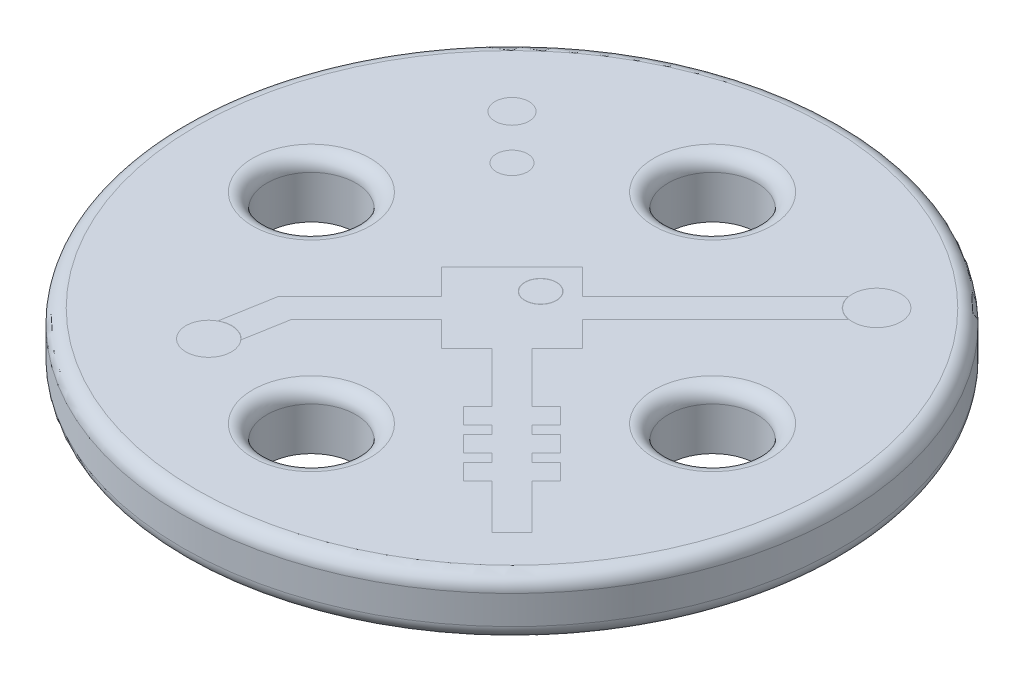
SolidWorks part; units mm, degrees
other "graphite_1"
other "blue_2"
other "white_6"
other "white_7"
other "white_10"
other "white_4"
other "white_2"
other "blue_1"
other "white_3"
other "white_9"
other "white_8"
other "white_5"
other "white"
ref_plane "Front Plane" through (0, 0, 0) normal (0, 0, 1) x (1, 0, 0)
ref_plane "Top Plane" through (0, 0, 0) normal (0, 1, 0) x (1, 0, 0)
ref_plane "Right Plane" through (0, 0, 0) normal (1, 0, 0) x (0, 0, -1)
sketch "Sketch1" plane through (0, 0, 0) normal (0, 1, 0) x (1, 0, 0)
  line L0 (0, 7) -> (0, 0) construction
  circle A0 centre (0, 0) radius 11.5
  circle A1 centre (0, 7) radius 1.55
  circle A2 centre (7, 0) radius 1.55
  circle A3 centre (0, -7) radius 1.55
  circle A4 centre (-7, 0) radius 1.55
  point P14 (0, 0)
  dimension "D1" = 23
  dimension "D2" = 3.1
  dimension "D3" = 7
  dimension "D4" = 4
extrude "Boss-Extrude1" add sketch "Sketch1" along normal blind 2
fillet "Fillet1" radius 0.5 6 edges at (-7, 2, 1.55) (7, 2, 1.55) (0, 2, 11.5) (0, 2, -5.45) (0, 2, 8.55) (0, 0, 11.5)
sketch "Sketch2" [suppressed] plane through (0, 2, 0) normal (0, 1, 0) x (1, 0, 0)
  line L0 (-2.4749, -2.4749) -> (2.4749, 2.4749) construction
  line L3 (-4.2426, -0.7071) -> (0.7071, 4.2426) construction
  line L4 (-0.7071, -4.2426) -> (4.2426, 0.7071) construction
  line L5 (0, 0) -> (23.072, 0) construction
  line L6 (-6.364, -2.1213) -> (-2.1213, -6.364) construction
  line L7 (-2.1213, -6.364) -> (6.364, 2.1213) construction
  line L8 (6.364, 2.1213) -> (2.1213, 6.364) construction
  line L9 (2.1213, 6.364) -> (-6.364, -2.1213) construction
  line L10 (-6.364, -2.1213) -> (6.364, 2.1213) construction
  line L11 (2.1213, 6.364) -> (6.364, 2.1213)
  line L12 (6.364, 2.1213) -> (4.9497, 0.7071)
  line L13 (2.1213, 6.364) -> (0.7071, 4.9497)
  line L14 (-6.364, -2.1213) -> (-4.9497, -0.7071)
  line L15 (-6.364, -2.1213) -> (-2.1213, -6.364)
  line L16 (-2.1213, -6.364) -> (-0.7071, -4.9497)
  circle A0 centre (-7, 0) radius 2.75 construction
  circle A1 centre (0, 7) radius 2.75 construction
  circle A2 centre (7, 0) radius 2.75 construction
  circle A3 centre (0, -7) radius 2.75 construction
  arc A6 (-4.2426, -0.7071) -> (-0.7071, -4.2426) centre (-2.4749, -2.4749) ccw construction
  arc A7 (4.2426, 0.7071) -> (0.7071, 4.2426) centre (2.4749, 2.4749) ccw construction
  circle A8 centre (0, 0) radius 5 construction
  arc A10 (-0.7071, -4.9497) -> (4.9497, 0.7071) centre (0, 0) ccw
  arc A12 (0.7071, 4.9497) -> (-4.9497, -0.7071) centre (0, 0) ccw
  point P13 (0, 0)
  dimension "D1" = 5.5
  dimension "D2" = 12
  dimension "D3" = 5
  dimension "D7" = 10
  dimension "D4" = 45
  dimension "D5" = 6
  dimension "D6" = 12
extrude "Cable hole" [suppressed] cut sketch "Sketch2" against normal through all
fillet "Fillet2" [suppressed] radius 1
sketch "GL_F_side_blue" plane through (0, 0, 0) normal (0, 1, 0) x (1, 0, 0)
  line L0 (4.1012, -5.7912) -> (3.5426, -5.2326)
  line L1 (3.5426, -5.2326) -> (4.0376, -4.7376)
  line L2 (4.0376, -4.7376) -> (3.7477, -4.4477)
  line L3 (3.7477, -4.4477) -> (3.2527, -4.9427)
  line L4 (3.2527, -4.9427) -> (2.6941, -4.3841)
  line L5 (2.6941, -4.3841) -> (3.1891, -3.8891)
  line L6 (3.1891, -3.8891) -> (1.2092, -1.9092)
  line L7 (1.2092, -1.9092) -> (1.3233, -1.795)
  line L8 (1.3233, -1.795) -> (-1.795, -1.795)
  line L9 (-1.795, -1.795) -> (-1.795, 1.3233)
  line L10 (-1.795, 1.3233) -> (-1.9092, 1.2092)
  line L11 (-1.9092, 1.2092) -> (-4.852, 4.1519)
  line L12 (-4.852, 4.1519) -> (-4.7161, 4.1794)
  line L13 (-4.7161, 4.1794) -> (-4.5701, 4.2398)
  line L14 (-4.5701, 4.2398) -> (-4.3805, 4.3805)
  line L15 (-4.3805, 4.3805) -> (-4.2398, 4.5701)
  line L16 (-4.2398, 4.5701) -> (-4.1794, 4.7161)
  line L17 (-4.1794, 4.7161) -> (-4.1519, 4.852)
  line L18 (-4.1519, 4.852) -> (-1.2092, 1.9092)
  line L19 (-1.2092, 1.9092) -> (-1.3233, 1.795)
  line L20 (-1.3233, 1.795) -> (1.3233, 1.795)
  line L21 (1.3233, 1.795) -> (1.2092, 1.9092)
  line L22 (1.2092, 1.9092) -> (5.6637, 6.3638)
  line L23 (5.6637, 6.3638) -> (5.6872, 6.2571)
  line L24 (5.6872, 6.2571) -> (5.7514, 6.1022)
  line L25 (5.7514, 6.1022) -> (5.9008, 5.9008)
  line L26 (5.9008, 5.9008) -> (6.1022, 5.7514)
  line L27 (6.1022, 5.7514) -> (6.2571, 5.6872)
  line L28 (6.2571, 5.6872) -> (6.3638, 5.6637)
  line L29 (6.3638, 5.6637) -> (1.9092, 1.2092)
  line L30 (1.9092, 1.2092) -> (1.795, 1.3233)
  line L31 (1.795, 1.3233) -> (1.795, -1.3233)
  line L32 (1.795, -1.3233) -> (1.9092, -1.2092)
  line L33 (1.9092, -1.2092) -> (3.8891, -3.1891)
  line L34 (3.8891, -3.1891) -> (4.3841, -2.6941)
  line L35 (4.3841, -2.6941) -> (4.9427, -3.2527)
  line L36 (4.9427, -3.2527) -> (4.4477, -3.7477)
  line L37 (4.4477, -3.7477) -> (4.7376, -4.0376)
  line L38 (4.7376, -4.0376) -> (5.2326, -3.5426)
  line L39 (5.2326, -3.5426) -> (5.7912, -4.1012)
  line L40 (5.7912, -4.1012) -> (5.2962, -4.5962)
  line L41 (5.2962, -4.5962) -> (6.9933, -6.2933)
  line L42 (6.9933, -6.2933) -> (6.2933, -6.9933)
  line L43 (6.2933, -6.9933) -> (4.5962, -5.2962)
  line L44 (4.5962, -5.2962) -> (4.1012, -5.7912)
  line L45 (-0.2962, 0.7941) -> (-0.2962, 0.9029)
  line L46 (-0.2962, 0.9029) -> (-0.3174, 1.0096)
  line L47 (-0.3174, 1.0096) -> (-0.359, 1.1102)
  line L48 (-0.359, 1.1102) -> (-0.4195, 1.2006)
  line L49 (-0.4195, 1.2006) -> (-0.4964, 1.2776)
  line L50 (-0.4964, 1.2776) -> (-0.5869, 1.338)
  line L51 (-0.5869, 1.338) -> (-0.6874, 1.3797)
  line L52 (-0.6874, 1.3797) -> (-0.7941, 1.4009)
  line L53 (-0.7941, 1.4009) -> (-0.9029, 1.4009)
  line L54 (-0.9029, 1.4009) -> (-1.0096, 1.3797)
  line L55 (-1.0096, 1.3797) -> (-1.1102, 1.338)
  line L56 (-1.1102, 1.338) -> (-1.2006, 1.2776)
  line L57 (-1.2006, 1.2776) -> (-1.2776, 1.2006)
  line L58 (-1.2776, 1.2006) -> (-1.338, 1.1102)
  line L59 (-1.338, 1.1102) -> (-1.3797, 1.0096)
  line L60 (-1.3797, 1.0096) -> (-1.4009, 0.9029)
  line L61 (-1.4009, 0.9029) -> (-1.4009, 0.7941)
  line L62 (-1.4009, 0.7941) -> (-1.3797, 0.6874)
  line L63 (-1.3797, 0.6874) -> (-1.338, 0.5869)
  line L64 (-1.338, 0.5869) -> (-1.2776, 0.4964)
  line L65 (-1.2776, 0.4964) -> (-1.2006, 0.4195)
  line L66 (-1.2006, 0.4195) -> (-1.1102, 0.359)
  line L67 (-1.1102, 0.359) -> (-1.0096, 0.3174)
  line L68 (-1.0096, 0.3174) -> (-0.9029, 0.2962)
  line L69 (-0.9029, 0.2962) -> (-0.7941, 0.2962)
  line L70 (-0.7941, 0.2962) -> (-0.6874, 0.3174)
  line L71 (-0.6874, 0.3174) -> (-0.5869, 0.359)
  line L72 (-0.5869, 0.359) -> (-0.4964, 0.4195)
  line L73 (-0.4964, 0.4195) -> (-0.4195, 0.4964)
  line L74 (-0.4195, 0.4964) -> (-0.359, 0.5869)
  line L75 (-0.359, 0.5869) -> (-0.3174, 0.6874)
  line L76 (-0.3174, 0.6874) -> (-0.2962, 0.7941)
extrude "GL_F_side_blue_cut" cut sketch "GL_F_side_blue" along normal blind 1.1 from offset 0.5 offset against normal yes
extrude "GL_F_side_blue_inlay" add sketch "GL_F_side_blue<2>" along normal blind 0.6 separate body
sketch "GL_F_side_blue<2>" plane through (0, 0, 0) normal (0, 1, 0) x (1, 0, 0) same geometry as "GL_F_side_blue"
sketch "GL_F_side_white" plane through (0, 0, 0) normal (0, 1, 0) x (1, 0, 0)
  line L0 (-5.628, -6.3839) -> (-5.6958, -6.4665)
  line L1 (-5.6958, -6.4665) -> (-5.7783, -6.5342)
  line L2 (-5.7783, -6.5342) -> (-5.8726, -6.5846)
  line L3 (-5.8726, -6.5846) -> (-5.9748, -6.6156)
  line L4 (-5.9748, -6.6156) -> (-6.0811, -6.6261)
  line L5 (-6.0811, -6.6261) -> (-6.1874, -6.6156)
  line L6 (-6.1874, -6.6156) -> (-6.2897, -6.5846)
  line L7 (-6.2897, -6.5846) -> (-6.3839, -6.5342)
  line L8 (-6.3839, -6.5342) -> (-6.4665, -6.4665)
  line L9 (-6.4665, -6.4665) -> (-6.5342, -6.3839)
  line L10 (-6.5342, -6.3839) -> (-6.5846, -6.2897)
  line L11 (-6.5846, -6.2897) -> (-6.6156, -6.1874)
  line L12 (-6.6156, -6.1874) -> (-6.6261, -6.0811)
  line L13 (-6.6261, -6.0811) -> (-6.6156, -5.9748)
  line L14 (-6.6156, -5.9748) -> (-6.5846, -5.8726)
  line L15 (-6.5846, -5.8726) -> (-6.5342, -5.7783)
  line L16 (-6.5342, -5.7783) -> (-6.4665, -5.6958)
  line L17 (-6.4665, -5.6958) -> (-6.3839, -5.628)
  line L18 (-6.3839, -5.628) -> (-6.2897, -5.5776)
  line L19 (-6.2897, -5.5776) -> (-6.1874, -5.5466)
  line L20 (-6.1874, -5.5466) -> (-6.0811, -5.5361)
  line L21 (-6.0811, -5.5361) -> (-5.9748, -5.5466)
  line L22 (-5.9748, -5.5466) -> (-5.8726, -5.5776)
  line L23 (-5.8726, -5.5776) -> (-5.7783, -5.628)
  line L24 (-5.7783, -5.628) -> (-5.6958, -5.6958)
  line L25 (-5.6958, -5.6958) -> (-5.628, -5.7783)
  line L26 (-5.628, -5.7783) -> (-5.5776, -5.8726)
  line L27 (-5.5776, -5.8726) -> (-5.5466, -5.9748)
  line L28 (-5.5466, -5.9748) -> (-5.5361, -6.0811)
  line L29 (-5.5361, -6.0811) -> (-5.5466, -6.1874)
  line L30 (-5.5466, -6.1874) -> (-5.5776, -6.2897)
  line L31 (-5.5776, -6.2897) -> (-5.628, -6.3839)
  line L32 (-3.7895, -4.5454) -> (-3.8573, -4.628)
  line L33 (-3.8573, -4.628) -> (-3.9399, -4.6958)
  line L34 (-3.9399, -4.6958) -> (-4.0341, -4.7461)
  line L35 (-4.0341, -4.7461) -> (-4.1363, -4.7771)
  line L36 (-4.1363, -4.7771) -> (-4.2426, -4.7876)
  line L37 (-4.2426, -4.7876) -> (-4.349, -4.7771)
  line L38 (-4.349, -4.7771) -> (-4.4512, -4.7461)
  line L39 (-4.4512, -4.7461) -> (-4.5454, -4.6958)
  line L40 (-4.5454, -4.6958) -> (-4.628, -4.628)
  line L41 (-4.628, -4.628) -> (-4.6958, -4.5454)
  line L42 (-4.6958, -4.5454) -> (-4.7461, -4.4512)
  line L43 (-4.7461, -4.4512) -> (-4.7771, -4.349)
  line L44 (-4.7771, -4.349) -> (-4.7876, -4.2426)
  line L45 (-4.7876, -4.2426) -> (-4.7771, -4.1363)
  line L46 (-4.7771, -4.1363) -> (-4.7461, -4.0341)
  line L47 (-4.7461, -4.0341) -> (-4.6958, -3.9399)
  line L48 (-4.6958, -3.9399) -> (-4.628, -3.8573)
  line L49 (-4.628, -3.8573) -> (-4.5454, -3.7895)
  line L50 (-4.5454, -3.7895) -> (-4.4512, -3.7391)
  line L51 (-4.4512, -3.7391) -> (-4.349, -3.7081)
  line L52 (-4.349, -3.7081) -> (-4.2426, -3.6977)
  line L53 (-4.2426, -3.6977) -> (-4.1363, -3.7081)
  line L54 (-4.1363, -3.7081) -> (-4.0341, -3.7391)
  line L55 (-4.0341, -3.7391) -> (-3.9399, -3.7895)
  line L56 (-3.9399, -3.7895) -> (-3.8573, -3.8573)
  line L57 (-3.8573, -3.8573) -> (-3.7895, -3.9399)
  line L58 (-3.7895, -3.9399) -> (-3.7391, -4.0341)
  line L59 (-3.7391, -4.0341) -> (-3.7081, -4.1363)
  line L60 (-3.7081, -4.1363) -> (-3.6977, -4.2426)
  line L61 (-3.6977, -4.2426) -> (-3.7081, -4.349)
  line L62 (-3.7081, -4.349) -> (-3.7391, -4.4512)
  line L63 (-3.7391, -4.4512) -> (-3.7895, -4.5454)
  line L64 (-0.3954, 0.5458) -> (-0.4632, 0.4632)
  line L65 (-0.4632, 0.4632) -> (-0.5458, 0.3954)
  line L66 (-0.5458, 0.3954) -> (-0.64, 0.345)
  line L67 (-0.64, 0.345) -> (-0.7422, 0.314)
  line L68 (-0.7422, 0.314) -> (-0.8485, 0.3036)
  line L69 (-0.8485, 0.3036) -> (-0.9548, 0.314)
  line L70 (-0.9548, 0.314) -> (-1.0571, 0.345)
  line L71 (-1.0571, 0.345) -> (-1.1513, 0.3954)
  line L72 (-1.1513, 0.3954) -> (-1.2339, 0.4632)
  line L73 (-1.2339, 0.4632) -> (-1.3017, 0.5458)
  line L74 (-1.3017, 0.5458) -> (-1.352, 0.64)
  line L75 (-1.352, 0.64) -> (-1.383, 0.7422)
  line L76 (-1.383, 0.7422) -> (-1.3935, 0.8485)
  line L77 (-1.3935, 0.8485) -> (-1.383, 0.9548)
  line L78 (-1.383, 0.9548) -> (-1.352, 1.0571)
  line L79 (-1.352, 1.0571) -> (-1.3017, 1.1513)
  line L80 (-1.3017, 1.1513) -> (-1.2339, 1.2339)
  line L81 (-1.2339, 1.2339) -> (-1.1513, 1.3017)
  line L82 (-1.1513, 1.3017) -> (-1.0571, 1.352)
  line L83 (-1.0571, 1.352) -> (-0.9548, 1.383)
  line L84 (-0.9548, 1.383) -> (-0.8485, 1.3935)
  line L85 (-0.8485, 1.3935) -> (-0.7422, 1.383)
  line L86 (-0.7422, 1.383) -> (-0.64, 1.352)
  line L87 (-0.64, 1.352) -> (-0.5458, 1.3017)
  line L88 (-0.5458, 1.3017) -> (-0.4632, 1.2339)
  line L89 (-0.4632, 1.2339) -> (-0.3954, 1.1513)
  line L90 (-0.3954, 1.1513) -> (-0.345, 1.0571)
  line L91 (-0.345, 1.0571) -> (-0.314, 0.9548)
  line L92 (-0.314, 0.9548) -> (-0.3036, 0.8485)
  line L93 (-0.3036, 0.8485) -> (-0.314, 0.7422)
  line L94 (-0.314, 0.7422) -> (-0.345, 0.64)
  line L95 (-0.345, 0.64) -> (-0.3954, 0.5458)
  line L96 (-4.3876, 4.3876) -> (-4.5081, 4.2887)
  line L97 (-4.5081, 4.2887) -> (-4.6455, 4.2153)
  line L98 (-4.6455, 4.2153) -> (-4.7947, 4.17)
  line L99 (-4.7947, 4.17) -> (-4.9497, 4.1548)
  line L100 (-4.9497, 4.1548) -> (-5.1048, 4.17)
  line L101 (-5.1048, 4.17) -> (-5.254, 4.2153)
  line L102 (-5.254, 4.2153) -> (-5.3914, 4.2887)
  line L103 (-5.3914, 4.2887) -> (-5.5119, 4.3876)
  line L104 (-5.5119, 4.3876) -> (-5.6107, 4.5081)
  line L105 (-5.6107, 4.5081) -> (-5.6842, 4.6455)
  line L106 (-5.6842, 4.6455) -> (-5.7294, 4.7947)
  line L107 (-5.7294, 4.7947) -> (-5.7447, 4.9497)
  line L108 (-5.7447, 4.9497) -> (-5.7294, 5.1048)
  line L109 (-5.7294, 5.1048) -> (-5.6842, 5.254)
  line L110 (-5.6842, 5.254) -> (-5.6107, 5.3914)
  line L111 (-5.6107, 5.3914) -> (-5.5119, 5.5119)
  line L112 (-5.5119, 5.5119) -> (-5.3914, 5.6107)
  line L113 (-5.3914, 5.6107) -> (-5.254, 5.6842)
  line L114 (-5.254, 5.6842) -> (-5.1048, 5.7294)
  line L115 (-5.1048, 5.7294) -> (-4.9497, 5.7447)
  line L116 (-4.9497, 5.7447) -> (-4.7947, 5.7294)
  line L117 (-4.7947, 5.7294) -> (-4.6455, 5.6842)
  line L118 (-4.6455, 5.6842) -> (-4.5081, 5.6107)
  line L119 (-4.5081, 5.6107) -> (-4.3876, 5.5119)
  line L120 (-4.3876, 5.5119) -> (-4.2887, 5.3914)
  line L121 (-4.2887, 5.3914) -> (-4.2153, 5.254)
  line L122 (-4.2153, 5.254) -> (-4.17, 5.1048)
  line L123 (-4.17, 5.1048) -> (-4.1548, 4.9497)
  line L124 (-4.1548, 4.9497) -> (-4.17, 4.7947)
  line L125 (-4.17, 4.7947) -> (-4.2153, 4.6455)
  line L126 (-4.2153, 4.6455) -> (-4.2887, 4.5081)
  line L127 (-4.2887, 4.5081) -> (-4.3876, 4.3876)
  line L128 (7.1029, 5.9079) -> (6.9748, 5.8028)
  line L129 (6.9748, 5.8028) -> (6.8287, 5.7247)
  line L130 (6.8287, 5.7247) -> (6.6702, 5.6766)
  line L131 (6.6702, 5.6766) -> (6.5054, 5.6604)
  line L132 (6.5054, 5.6604) -> (6.3405, 5.6766)
  line L133 (6.3405, 5.6766) -> (6.182, 5.7247)
  line L134 (6.182, 5.7247) -> (6.0359, 5.8028)
  line L135 (6.0359, 5.8028) -> (5.9079, 5.9079)
  line L136 (5.9079, 5.9079) -> (5.8028, 6.0359)
  line L137 (5.8028, 6.0359) -> (5.7247, 6.182)
  line L138 (5.7247, 6.182) -> (5.6766, 6.3405)
  line L139 (5.6766, 6.3405) -> (5.6604, 6.5054)
  line L140 (5.6604, 6.5054) -> (5.6766, 6.6702)
  line L141 (5.6766, 6.6702) -> (5.7247, 6.8287)
  line L142 (5.7247, 6.8287) -> (5.8028, 6.9748)
  line L143 (5.8028, 6.9748) -> (5.9079, 7.1029)
  line L144 (5.9079, 7.1029) -> (6.0359, 7.208)
  line L145 (6.0359, 7.208) -> (6.182, 7.286)
  line L146 (6.182, 7.286) -> (6.3405, 7.3341)
  line L147 (6.3405, 7.3341) -> (6.5054, 7.3504)
  line L148 (6.5054, 7.3504) -> (6.6702, 7.3341)
  line L149 (6.6702, 7.3341) -> (6.8287, 7.286)
  line L150 (6.8287, 7.286) -> (6.9748, 7.208)
  line L151 (6.9748, 7.208) -> (7.1029, 7.1029)
  line L152 (7.1029, 7.1029) -> (7.208, 6.9748)
  line L153 (7.208, 6.9748) -> (7.286, 6.8287)
  line L154 (7.286, 6.8287) -> (7.3341, 6.6702)
  line L155 (7.3341, 6.6702) -> (7.3504, 6.5054)
  line L156 (7.3504, 6.5054) -> (7.3341, 6.3405)
  line L157 (7.3341, 6.3405) -> (7.286, 6.182)
  line L158 (7.286, 6.182) -> (7.208, 6.0359)
  line L159 (7.208, 6.0359) -> (7.1029, 5.9079)
extrude "GL_F_side_white_cut" cut sketch "GL_F_side_white" along normal blind 1.1 from offset 0.5 offset against normal yes
extrude "GL_F_side_white_inlay" add sketch "GL_F_side_white<2>" along normal blind 0.6 separate body
sketch "GL_F_side_white<2>" plane through (0, 0, 0) normal (0, 1, 0) x (1, 0, 0) same geometry as "GL_F_side_white"
sketch "GL_E_side_blue" plane through (0, 0, 0) normal (0, 1, 0) x (1, 0, 0)
  line L0 (4.3841, -6.074) -> (3.8254, -5.5154)
  line L1 (3.8254, -5.5154) -> (4.3204, -5.0205)
  line L2 (4.3204, -5.0205) -> (4.0305, -4.7305)
  line L3 (4.0305, -4.7305) -> (3.5355, -5.2255)
  line L4 (3.5355, -5.2255) -> (2.9769, -4.6669)
  line L5 (2.9769, -4.6669) -> (3.4719, -4.1719)
  line L6 (3.4719, -4.1719) -> (3.182, -3.882)
  line L7 (3.182, -3.882) -> (2.687, -4.377)
  line L8 (2.687, -4.377) -> (2.1284, -3.8184)
  line L9 (2.1284, -3.8184) -> (2.6234, -3.3234)
  line L10 (2.6234, -3.3234) -> (0.8839, -1.5839)
  line L11 (0.8839, -1.5839) -> (0, -2.4678)
  line L12 (0, -2.4678) -> (-0.8839, -1.5839)
  line L13 (-0.8839, -1.5839) -> (-3.4994, -4.1994)
  line L14 (-3.4994, -4.1994) -> (-3.7618, -5.6882)
  line L15 (-3.7618, -5.6882) -> (-3.8485, -5.6032)
  line L16 (-3.8485, -5.6032) -> (-3.9798, -5.5155)
  line L17 (-3.9798, -5.5155) -> (-4.202, -5.436)
  line L18 (-4.202, -5.436) -> (-4.3592, -5.4205)
  line L19 (-4.3592, -5.4205) -> (-4.5164, -5.436)
  line L20 (-4.5164, -5.436) -> (-4.7368, -5.5165)
  line L21 (-4.7368, -5.5165) -> (-4.4202, -3.7202)
  line L22 (-4.4202, -3.7202) -> (-1.5839, -0.8839)
  line L23 (-1.5839, -0.8839) -> (-2.4678, 0)
  line L24 (-2.4678, 0) -> (0, 2.4678)
  line L25 (0, 2.4678) -> (0.8839, 1.5839)
  line L26 (0.8839, 1.5839) -> (5.5223, 6.2223)
  line L27 (5.5223, 6.2223) -> (5.5458, 6.1157)
  line L28 (5.5458, 6.1157) -> (5.6099, 5.9608)
  line L29 (5.6099, 5.9608) -> (5.7593, 5.7593)
  line L30 (5.7593, 5.7593) -> (5.9608, 5.6099)
  line L31 (5.9608, 5.6099) -> (6.1157, 5.5458)
  line L32 (6.1157, 5.5458) -> (6.2223, 5.5223)
  line L33 (6.2223, 5.5223) -> (1.5839, 0.8839)
  line L34 (1.5839, 0.8839) -> (2.4678, 0)
  line L35 (2.4678, 0) -> (1.5839, -0.8839)
  line L36 (1.5839, -0.8839) -> (3.3234, -2.6234)
  line L37 (3.3234, -2.6234) -> (3.8184, -2.1284)
  line L38 (3.8184, -2.1284) -> (4.377, -2.687)
  line L39 (4.377, -2.687) -> (3.882, -3.182)
  line L40 (3.882, -3.182) -> (4.1719, -3.4719)
  line L41 (4.1719, -3.4719) -> (4.6669, -2.9769)
  line L42 (4.6669, -2.9769) -> (5.2255, -3.5355)
  line L43 (5.2255, -3.5355) -> (4.7305, -4.0305)
  line L44 (4.7305, -4.0305) -> (5.0205, -4.3204)
  line L45 (5.0205, -4.3204) -> (5.5154, -3.8254)
  line L46 (5.5154, -3.8254) -> (6.074, -4.3841)
  line L47 (6.074, -4.3841) -> (5.5791, -4.879)
  line L48 (5.5791, -4.879) -> (7.1347, -6.4347)
  line L49 (7.1347, -6.4347) -> (6.4347, -7.1347)
  line L50 (6.4347, -7.1347) -> (4.879, -5.5791)
  line L51 (4.879, -5.5791) -> (4.3841, -6.074)
  line L52 (0.5524, 0.9456) -> (0.5524, 1.0544)
  line L53 (0.5524, 1.0544) -> (0.5311, 1.1611)
  line L54 (0.5311, 1.1611) -> (0.4895, 1.2616)
  line L55 (0.4895, 1.2616) -> (0.429, 1.3521)
  line L56 (0.429, 1.3521) -> (0.3521, 1.429)
  line L57 (0.3521, 1.429) -> (0.2616, 1.4895)
  line L58 (0.2616, 1.4895) -> (0.1611, 1.5311)
  line L59 (0.1611, 1.5311) -> (0.0544, 1.5524)
  line L60 (0.0544, 1.5524) -> (-0.0544, 1.5524)
  line L61 (-0.0544, 1.5524) -> (-0.1611, 1.5311)
  line L62 (-0.1611, 1.5311) -> (-0.2616, 1.4895)
  line L63 (-0.2616, 1.4895) -> (-0.3521, 1.429)
  line L64 (-0.3521, 1.429) -> (-0.429, 1.3521)
  line L65 (-0.429, 1.3521) -> (-0.4895, 1.2616)
  line L66 (-0.4895, 1.2616) -> (-0.5311, 1.1611)
  line L67 (-0.5311, 1.1611) -> (-0.5524, 1.0544)
  line L68 (-0.5524, 1.0544) -> (-0.5524, 0.9456)
  line L69 (-0.5524, 0.9456) -> (-0.5311, 0.8389)
  line L70 (-0.5311, 0.8389) -> (-0.4895, 0.7384)
  line L71 (-0.4895, 0.7384) -> (-0.429, 0.6479)
  line L72 (-0.429, 0.6479) -> (-0.3521, 0.571)
  line L73 (-0.3521, 0.571) -> (-0.2616, 0.5105)
  line L74 (-0.2616, 0.5105) -> (-0.1611, 0.4689)
  line L75 (-0.1611, 0.4689) -> (-0.0544, 0.4476)
  line L76 (-0.0544, 0.4476) -> (0.0544, 0.4476)
  line L77 (0.0544, 0.4476) -> (0.1611, 0.4689)
  line L78 (0.1611, 0.4689) -> (0.2616, 0.5105)
  line L79 (0.2616, 0.5105) -> (0.3521, 0.571)
  line L80 (0.3521, 0.571) -> (0.429, 0.6479)
  line L81 (0.429, 0.6479) -> (0.4895, 0.7384)
  line L82 (0.4895, 0.7384) -> (0.5311, 0.8389)
  line L83 (0.5311, 0.8389) -> (0.5524, 0.9456)
extrude "GL_E_side_blue_cut" cut sketch "GL_E_side_blue" along normal blind 1.1 from offset 1.4
extrude "GL_E_side_blue_inlay" add sketch "GL_E_side_blue<2>" along normal blind 0.6 from offset 1.4 separate body
sketch "GL_E_side_blue<2>" plane through (0, 0, 0) normal (0, 1, 0) x (1, 0, 0) same geometry as "GL_E_side_blue"
sketch "GL_E_side_white" plane through (0, 0, 0) normal (0, 1, 0) x (1, 0, 0)
  line L0 (-3.6982, -6.6672) -> (-3.797, -6.7877)
  line L1 (-3.797, -6.7877) -> (-3.9175, -6.8866)
  line L2 (-3.9175, -6.8866) -> (-4.055, -6.96)
  line L3 (-4.055, -6.96) -> (-4.2041, -7.0053)
  line L4 (-4.2041, -7.0053) -> (-4.3592, -7.0205)
  line L5 (-4.3592, -7.0205) -> (-4.5143, -7.0053)
  line L6 (-4.5143, -7.0053) -> (-4.6634, -6.96)
  line L7 (-4.6634, -6.96) -> (-4.8008, -6.8866)
  line L8 (-4.8008, -6.8866) -> (-4.9213, -6.7877)
  line L9 (-4.9213, -6.7877) -> (-5.0202, -6.6672)
  line L10 (-5.0202, -6.6672) -> (-5.0936, -6.5298)
  line L11 (-5.0936, -6.5298) -> (-5.1389, -6.3806)
  line L12 (-5.1389, -6.3806) -> (-5.1542, -6.2256)
  line L13 (-5.1542, -6.2256) -> (-5.1389, -6.0705)
  line L14 (-5.1389, -6.0705) -> (-5.0936, -5.9213)
  line L15 (-5.0936, -5.9213) -> (-5.0202, -5.7839)
  line L16 (-5.0202, -5.7839) -> (-4.9213, -5.6634)
  line L17 (-4.9213, -5.6634) -> (-4.8008, -5.5646)
  line L18 (-4.8008, -5.5646) -> (-4.6634, -5.4911)
  line L19 (-4.6634, -5.4911) -> (-4.5143, -5.4459)
  line L20 (-4.5143, -5.4459) -> (-4.3592, -5.4306)
  line L21 (-4.3592, -5.4306) -> (-4.2041, -5.4459)
  line L22 (-4.2041, -5.4459) -> (-4.055, -5.4911)
  line L23 (-4.055, -5.4911) -> (-3.9175, -5.5646)
  line L24 (-3.9175, -5.5646) -> (-3.797, -5.6634)
  line L25 (-3.797, -5.6634) -> (-3.6982, -5.7839)
  line L26 (-3.6982, -5.7839) -> (-3.6247, -5.9213)
  line L27 (-3.6247, -5.9213) -> (-3.5795, -6.0705)
  line L28 (-3.5795, -6.0705) -> (-3.5642, -6.2256)
  line L29 (-3.5642, -6.2256) -> (-3.5795, -6.3806)
  line L30 (-3.5795, -6.3806) -> (-3.6247, -6.5298)
  line L31 (-3.6247, -6.5298) -> (-3.6982, -6.6672)
  line L32 (0.4531, 0.6972) -> (0.3854, 0.6146)
  line L33 (0.3854, 0.6146) -> (0.3028, 0.5469)
  line L34 (0.3028, 0.5469) -> (0.2086, 0.4965)
  line L35 (0.2086, 0.4965) -> (0.1063, 0.4655)
  line L36 (0.1063, 0.4655) -> (0, 0.455)
  line L37 (0, 0.455) -> (-0.1063, 0.4655)
  line L38 (-0.1063, 0.4655) -> (-0.2086, 0.4965)
  line L39 (-0.2086, 0.4965) -> (-0.3028, 0.5469)
  line L40 (-0.3028, 0.5469) -> (-0.3854, 0.6146)
  line L41 (-0.3854, 0.6146) -> (-0.4531, 0.6972)
  line L42 (-0.4531, 0.6972) -> (-0.5035, 0.7914)
  line L43 (-0.5035, 0.7914) -> (-0.5345, 0.8937)
  line L44 (-0.5345, 0.8937) -> (-0.545, 1)
  line L45 (-0.545, 1) -> (-0.5345, 1.1063)
  line L46 (-0.5345, 1.1063) -> (-0.5035, 1.2086)
  line L47 (-0.5035, 1.2086) -> (-0.4531, 1.3028)
  line L48 (-0.4531, 1.3028) -> (-0.3854, 1.3854)
  line L49 (-0.3854, 1.3854) -> (-0.3028, 1.4531)
  line L50 (-0.3028, 1.4531) -> (-0.2086, 1.5035)
  line L51 (-0.2086, 1.5035) -> (-0.1063, 1.5345)
  line L52 (-0.1063, 1.5345) -> (0, 1.545)
  line L53 (0, 1.545) -> (0.1063, 1.5345)
  line L54 (0.1063, 1.5345) -> (0.2086, 1.5035)
  line L55 (0.2086, 1.5035) -> (0.3028, 1.4531)
  line L56 (0.3028, 1.4531) -> (0.3854, 1.3854)
  line L57 (0.3854, 1.3854) -> (0.4531, 1.3028)
  line L58 (0.4531, 1.3028) -> (0.5035, 1.2086)
  line L59 (0.5035, 1.2086) -> (0.5345, 1.1063)
  line L60 (0.5345, 1.1063) -> (0.545, 1)
  line L61 (0.545, 1) -> (0.5345, 0.8937)
  line L62 (0.5345, 0.8937) -> (0.5035, 0.7914)
  line L63 (0.5035, 0.7914) -> (0.4531, 0.6972)
  line L64 (-3.9309, 4.0813) -> (-3.9987, 3.9987)
  line L65 (-3.9987, 3.9987) -> (-4.0813, 3.9309)
  line L66 (-4.0813, 3.9309) -> (-4.1755, 3.8806)
  line L67 (-4.1755, 3.8806) -> (-4.2777, 3.8496)
  line L68 (-4.2777, 3.8496) -> (-4.3841, 3.8391)
  line L69 (-4.3841, 3.8391) -> (-4.4904, 3.8496)
  line L70 (-4.4904, 3.8496) -> (-4.5926, 3.8806)
  line L71 (-4.5926, 3.8806) -> (-4.6868, 3.9309)
  line L72 (-4.6868, 3.9309) -> (-4.7694, 3.9987)
  line L73 (-4.7694, 3.9987) -> (-4.8372, 4.0813)
  line L74 (-4.8372, 4.0813) -> (-4.8876, 4.1755)
  line L75 (-4.8876, 4.1755) -> (-4.9186, 4.2777)
  line L76 (-4.9186, 4.2777) -> (-4.929, 4.3841)
  line L77 (-4.929, 4.3841) -> (-4.9186, 4.4904)
  line L78 (-4.9186, 4.4904) -> (-4.8876, 4.5926)
  line L79 (-4.8876, 4.5926) -> (-4.8372, 4.6868)
  line L80 (-4.8372, 4.6868) -> (-4.7694, 4.7694)
  line L81 (-4.7694, 4.7694) -> (-4.6868, 4.8372)
  line L82 (-4.6868, 4.8372) -> (-4.5926, 4.8876)
  line L83 (-4.5926, 4.8876) -> (-4.4904, 4.9186)
  line L84 (-4.4904, 4.9186) -> (-4.3841, 4.929)
  line L85 (-4.3841, 4.929) -> (-4.2777, 4.9186)
  line L86 (-4.2777, 4.9186) -> (-4.1755, 4.8876)
  line L87 (-4.1755, 4.8876) -> (-4.0813, 4.8372)
  line L88 (-4.0813, 4.8372) -> (-3.9987, 4.7694)
  line L89 (-3.9987, 4.7694) -> (-3.9309, 4.6868)
  line L90 (-3.9309, 4.6868) -> (-3.8806, 4.5926)
  line L91 (-3.8806, 4.5926) -> (-3.8496, 4.4904)
  line L92 (-3.8496, 4.4904) -> (-3.8391, 4.3841)
  line L93 (-3.8391, 4.3841) -> (-3.8496, 4.2777)
  line L94 (-3.8496, 4.2777) -> (-3.8806, 4.1755)
  line L95 (-3.8806, 4.1755) -> (-3.9309, 4.0813)
  line L96 (-5.519, 5.519) -> (-5.6091, 5.445)
  line L97 (-5.6091, 5.445) -> (-5.712, 5.39)
  line L98 (-5.712, 5.39) -> (-5.8236, 5.3562)
  line L99 (-5.8236, 5.3562) -> (-5.9397, 5.3447)
  line L100 (-5.9397, 5.3447) -> (-6.0558, 5.3562)
  line L101 (-6.0558, 5.3562) -> (-6.1674, 5.39)
  line L102 (-6.1674, 5.39) -> (-6.2702, 5.445)
  line L103 (-6.2702, 5.445) -> (-6.3604, 5.519)
  line L104 (-6.3604, 5.519) -> (-6.4344, 5.6091)
  line L105 (-6.4344, 5.6091) -> (-6.4894, 5.712)
  line L106 (-6.4894, 5.712) -> (-6.5232, 5.8236)
  line L107 (-6.5232, 5.8236) -> (-6.5347, 5.9397)
  line L108 (-6.5347, 5.9397) -> (-6.5232, 6.0558)
  line L109 (-6.5232, 6.0558) -> (-6.4894, 6.1674)
  line L110 (-6.4894, 6.1674) -> (-6.4344, 6.2702)
  line L111 (-6.4344, 6.2702) -> (-6.3604, 6.3604)
  line L112 (-6.3604, 6.3604) -> (-6.2702, 6.4344)
  line L113 (-6.2702, 6.4344) -> (-6.1674, 6.4894)
  line L114 (-6.1674, 6.4894) -> (-6.0558, 6.5232)
  line L115 (-6.0558, 6.5232) -> (-5.9397, 6.5347)
  line L116 (-5.9397, 6.5347) -> (-5.8236, 6.5232)
  line L117 (-5.8236, 6.5232) -> (-5.712, 6.4894)
  line L118 (-5.712, 6.4894) -> (-5.6091, 6.4344)
  line L119 (-5.6091, 6.4344) -> (-5.519, 6.3604)
  line L120 (-5.519, 6.3604) -> (-5.445, 6.2702)
  line L121 (-5.445, 6.2702) -> (-5.39, 6.1674)
  line L122 (-5.39, 6.1674) -> (-5.3562, 6.0558)
  line L123 (-5.3562, 6.0558) -> (-5.3447, 5.9397)
  line L124 (-5.3447, 5.9397) -> (-5.3562, 5.8236)
  line L125 (-5.3562, 5.8236) -> (-5.39, 5.712)
  line L126 (-5.39, 5.712) -> (-5.445, 5.6091)
  line L127 (-5.445, 5.6091) -> (-5.519, 5.519)
  line L128 (6.9614, 5.7665) -> (6.8334, 5.6614)
  line L129 (6.8334, 5.6614) -> (6.6873, 5.5833)
  line L130 (6.6873, 5.5833) -> (6.5288, 5.5352)
  line L131 (6.5288, 5.5352) -> (6.364, 5.519)
  line L132 (6.364, 5.519) -> (6.1991, 5.5352)
  line L133 (6.1991, 5.5352) -> (6.0406, 5.5833)
  line L134 (6.0406, 5.5833) -> (5.8945, 5.6614)
  line L135 (5.8945, 5.6614) -> (5.7665, 5.7665)
  line L136 (5.7665, 5.7665) -> (5.6614, 5.8945)
  line L137 (5.6614, 5.8945) -> (5.5833, 6.0406)
  line L138 (5.5833, 6.0406) -> (5.5352, 6.1991)
  line L139 (5.5352, 6.1991) -> (5.519, 6.364)
  line L140 (5.519, 6.364) -> (5.5352, 6.5288)
  line L141 (5.5352, 6.5288) -> (5.5833, 6.6873)
  line L142 (5.5833, 6.6873) -> (5.6614, 6.8334)
  line L143 (5.6614, 6.8334) -> (5.7665, 6.9614)
  line L144 (5.7665, 6.9614) -> (5.8945, 7.0665)
  line L145 (5.8945, 7.0665) -> (6.0406, 7.1446)
  line L146 (6.0406, 7.1446) -> (6.1991, 7.1927)
  line L147 (6.1991, 7.1927) -> (6.364, 7.2089)
  line L148 (6.364, 7.2089) -> (6.5288, 7.1927)
  line L149 (6.5288, 7.1927) -> (6.6873, 7.1446)
  line L150 (6.6873, 7.1446) -> (6.8334, 7.0665)
  line L151 (6.8334, 7.0665) -> (6.9614, 6.9614)
  line L152 (6.9614, 6.9614) -> (7.0665, 6.8334)
  line L153 (7.0665, 6.8334) -> (7.1446, 6.6873)
  line L154 (7.1446, 6.6873) -> (7.1927, 6.5288)
  line L155 (7.1927, 6.5288) -> (7.2089, 6.364)
  line L156 (7.2089, 6.364) -> (7.1927, 6.1991)
  line L157 (7.1927, 6.1991) -> (7.1446, 6.0406)
  line L158 (7.1446, 6.0406) -> (7.0665, 5.8945)
  line L159 (7.0665, 5.8945) -> (6.9614, 5.7665)
extrude "GL_E_side_white_cut" cut sketch "GL_E_side_white" along normal blind 1.1 from offset 1.4
extrude "GL_E_side_white_inlay" add sketch "GL_E_side_white<2>" along normal blind 0.6 from offset 1.4 separate body
sketch "GL_E_side_white<2>" plane through (0, 0, 0) normal (0, 1, 0) x (1, 0, 0) same geometry as "GL_E_side_white"
